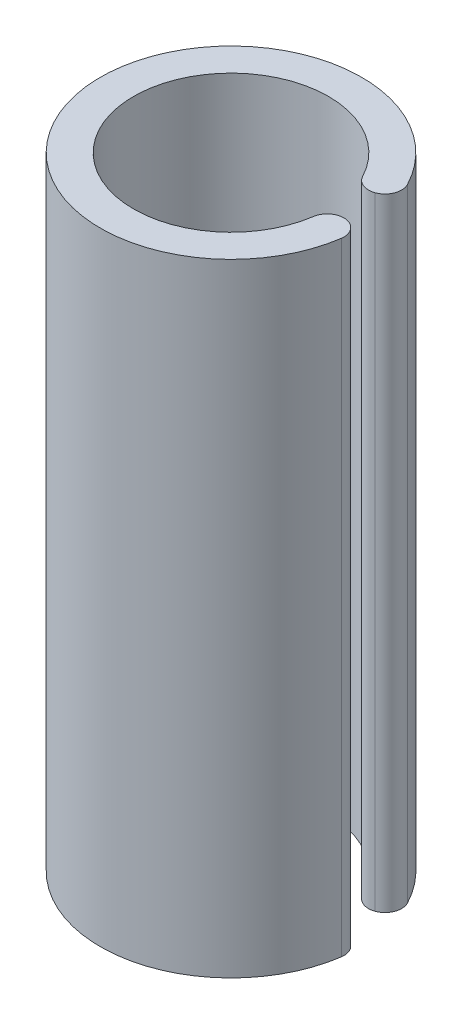
SolidWorks part; units mm, degrees
ref_plane "Front Plane" through (0, 0, 0) normal (0, 0, 1) x (1, 0, 0)
ref_plane "Top Plane" through (0, 0, 0) normal (0, 1, 0) x (1, 0, 0)
ref_plane "Right Plane" through (0, 0, 0) normal (1, 0, 0) x (0, 0, -1)
sketch "Sketch1" plane through (0, 0, 0) normal (0, 1, 0) x (1, 0, 0)
  line L1 (2.2196, 0.7721) -> (2.971, 1.0467)
  line L3 (2.35, 0) -> (3.15, 0)
  arc A0 (2.971, 1.0467) -> (3.15, 0) centre (0, 0) ccw
  arc A1 (2.2196, 0.7721) -> (2.35, 0) centre (0, 0) ccw
  dimension "D1" = 4.7
  dimension "D2" = 6.3
extrude "Boss-Extrude1" add sketch "Sketch1" along normal blind 15
fillet "Fillet1" radius 0.4 4 edges at (3.15, 7.5, 0) (2.35, 7.5, 0) (2.2196, 7.5, -0.7721) (2.971, 7.5, -1.0467)
